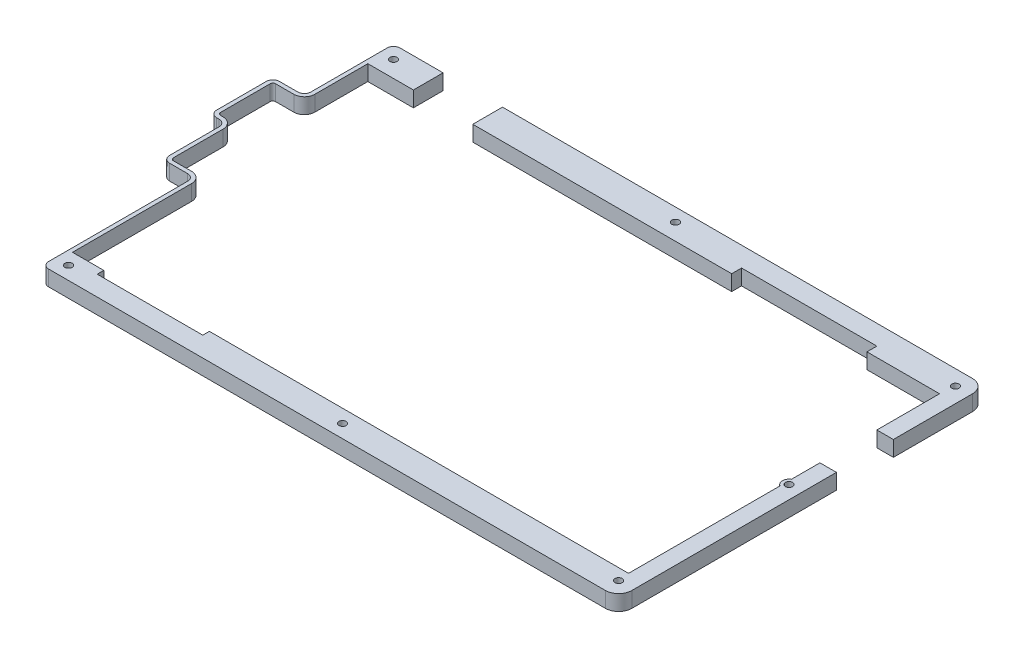
SolidWorks part; units mm, degrees
ref_plane "Front Plane" through (0, 0, 0) normal (0, 0, 1) x (1, 0, 0)
ref_plane "Top Plane" through (0, 0, 0) normal (0, 1, 0) x (1, 0, 0)
ref_plane "Right Plane" through (0, 0, 0) normal (1, 0, 0) x (0, 0, -1)
sketch "Sketch1" plane through (0, 0, 0) normal (0, 1, 0) x (1, 0, 0)
  line L0 (138.4196, 31.7518) -> (125.4196, 31.7518)
  line L1 (-35.0204, 31.7518) -> (107.4196, 31.7518)
  line L2 (140.4196, 29.7518) -> (140.4196, 6.7018)
  line L3 (-34.0204, 3.7518) -> (-34.0204, 22.7518)
  line L4 (136.4596, 27.7518) -> (136.4396, 27.7518)
  line L5 (142.4196, 4.7018) -> (147.9496, 4.7018)
  line L6 (-34.0204, 22.7518) -> (-12.0204, 22.7518)
  line L8 (149.9496, 2.7018) -> (149.9496, -12.3482)
  line L11 (147.9496, -14.3482) -> (147.1896, -14.3482)
  line L14 (145.1896, -16.3482) -> (145.1896, -31.3982)
  line L17 (143.1896, -33.3982) -> (137.6696, -33.3982)
  line L20 (135.6696, -35.3982) -> (135.6696, -77.4982)
  line L21 (-34.0204, -25.6003) -> (-34.0204, -71.4982)
  line L23 (133.6696, -79.4982) -> (-35.0204, -79.4982)
  line L28 (-39.0204, 27.7518) -> (-39.0204, 3.7518)
  line L31 (-34.0204, 3.7518) -> (-39.0204, 3.7518)
  line L32 (-34.0204, -13.4982) -> (-39.0204, -13.4982)
  line L33 (-39.0204, -75.4982) -> (-39.0204, -13.4982)
  line L34 (-34.0204, -71.4982) -> (92.9796, -71.4982)
  line L35 (92.9796, -71.4982) -> (92.9796, -73.4982)
  line L36 (92.9796, -73.4982) -> (124.9796, -73.4982)
  line L37 (124.9796, -73.4982) -> (124.9796, -71.4982)
  line L39 (134.4706, -35.3982) -> (134.4706, -71.4982)
  line L40 (134.4706, -71.4982) -> (124.9796, -71.4982)
  line L41 (137.6696, -32.1992) -> (143.1896, -32.1992)
  line L42 (-34.0204, -13.4982) -> (-34.0204, -22.1362)
  line L43 (143.9906, -31.3982) -> (143.9906, -16.3482)
  line L44 (-12.0204, 22.7518) -> (-12.0204, 25.7518)
  line L45 (147.1896, -13.1492) -> (147.9496, -13.1492)
  line L46 (148.7506, -12.3482) -> (148.7506, 2.7018)
  line L47 (-12.0204, 25.7518) -> (28.9796, 25.7518)
  line L48 (28.9796, 25.7518) -> (28.9796, 22.7518)
  line L49 (28.9796, 22.7518) -> (107.4196, 22.7518)
  line L50 (147.9496, 3.5027) -> (142.4196, 3.5027)
  line L51 (107.4196, 22.7518) -> (107.4196, 31.7518)
  line L52 (139.2206, 6.7018) -> (139.2206, 22.7518)
  line L53 (125.4196, 31.7518) -> (125.4196, 22.7518)
  line L54 (139.2206, 22.7518) -> (125.4196, 22.7518)
  arc A0 (138.4196, 31.7518) -> (140.4196, 29.7518) centre (138.4196, 29.7518) cw
  arc A1 (140.4196, 6.7018) -> (142.4196, 4.7018) centre (142.4196, 6.7018) ccw
  arc A2 (149.9496, 2.7018) -> (147.9496, 4.7018) centre (147.9496, 2.7018) ccw
  arc A3 (149.9496, -12.3482) -> (147.9496, -14.3482) centre (147.9496, -12.3482) cw
  arc A4 (147.1896, -14.3482) -> (145.1896, -16.3482) centre (147.1896, -16.3482) ccw
  arc A5 (145.1896, -31.3982) -> (143.1896, -33.3982) centre (143.1896, -31.3982) cw
  arc A6 (-35.0204, 31.7518) -> (-39.0204, 27.7518) centre (-35.0204, 27.7518) ccw
  arc A7 (-39.0204, -75.4982) -> (-35.0204, -79.4982) centre (-35.0204, -75.4982) ccw
  arc A8 (133.6696, -79.4982) -> (135.6696, -77.4982) centre (133.6696, -77.4982) ccw
  arc A9 (135.6696, -35.3982) -> (137.6696, -33.3982) centre (137.6696, -35.3982) cw
  circle A10 centre (-34.4204, 27.1518) radius 1.1
  circle A11 centre (51.0096, 27.7518) radius 1.1
  circle A12 centre (136.4396, 27.7518) radius 1.1
  circle A13 centre (-34.4204, -74.8982) radius 1.1
  circle A14 centre (48.6296, -75.4982) radius 1.1
  circle A15 centre (131.6496, -75.4982) radius 1.1
  circle A16 centre (-35.0204, -23.8682) radius 1.1
  arc A27 (-34.0204, -22.1362) -> (-34.0204, -25.6003) centre (-35.0204, -23.8682) cw
  arc A28 (139.2206, 6.7018) -> (142.4196, 3.5027) centre (142.4196, 6.7018) ccw
  arc A29 (147.9496, 3.5027) -> (148.7506, 2.7018) centre (147.9496, 2.7018) cw
  arc A30 (148.7506, -12.3482) -> (147.9496, -13.1492) centre (147.9496, -12.3482) cw
  arc A31 (147.1896, -13.1492) -> (143.9906, -16.3482) centre (147.1896, -16.3482) ccw
  arc A32 (143.9906, -31.3982) -> (143.1896, -32.1992) centre (143.1896, -31.3982) cw
  arc A33 (137.6696, -32.1992) -> (134.4706, -35.3982) centre (137.6696, -35.3982) ccw
extrude "Boss-Extrude2" add sketch "Sketch1" against normal blind 4.7 contours L41 A33 L39 L40 L37 L36 L35 L34 L21 A27 L42 L32 L33 A7 L23 A8 L20 A9 L17 A5 L14 A4 L11 A3 L8 A2 L5 A1 L2 A0 L0 L53 L54 L52 A28 L50 A29 L46 A30 L45 A31 L43 A32 A12 A13 A14 A15 | L1 A6 L28 L31 L3 L6 L44 L47 L48 L49 L51 A11 A10 region at (138.2833, 0, -29.6154) region at (31.7683, 0, -26.4895)
move or copy body "Body-Move/Copy1" bodies to move or copy 105 104 copy no rotation origin (55.4646, -2.35, 0) rotation axis (0, 0, 1) rotation angle 180
